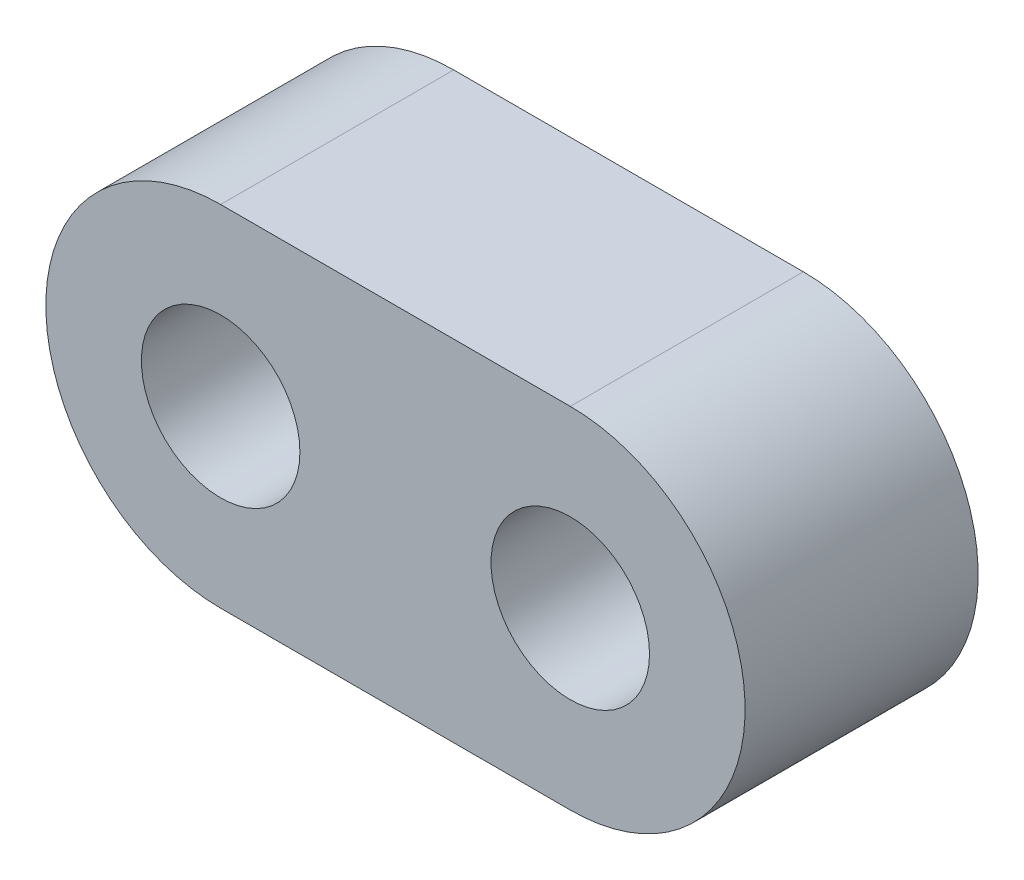
SolidWorks part; units mm, degrees
ref_plane "Front Plane" through (0, 0, 0) normal (0, 0, 1) x (1, 0, 0)
ref_plane "Top Plane" through (0, 0, 0) normal (0, 1, 0) x (1, 0, 0)
ref_plane "Right Plane" through (0, 0, 0) normal (1, 0, 0) x (0, 0, -1)
sketch "Sketch1" plane through (0, 0, 0) normal (0, 0, 1) x (1, 0, 0)
  line L0 (0, 0) -> (9.525, 0) construction
  line L1 (0, 4.7625) -> (9.525, 4.7625)
  line L2 (0, -4.7625) -> (9.525, -4.7625)
  arc A0 (0, 4.7625) -> (0, -4.7625) centre (0, 0) ccw
  arc A1 (9.525, -4.7625) -> (9.525, 4.7625) centre (9.525, 0) ccw
  circle A2 centre (9.525, 0) radius 2.159
  circle A3 centre (0, 0) radius 2.159
  point P3 (4.7625, 0)
  dimension "D2" = 9.525
  dimension "D3" = 4.318
  dimension "D1" = 9.525
extrude "Boss-Extrude1" add sketch "Sketch1" along normal blind 6.35
sketch "Sketch2" plane through (0, 0, 6.35) normal (0, 0, 1) x (1, 0, 0)
  point P0 (0, 0)
